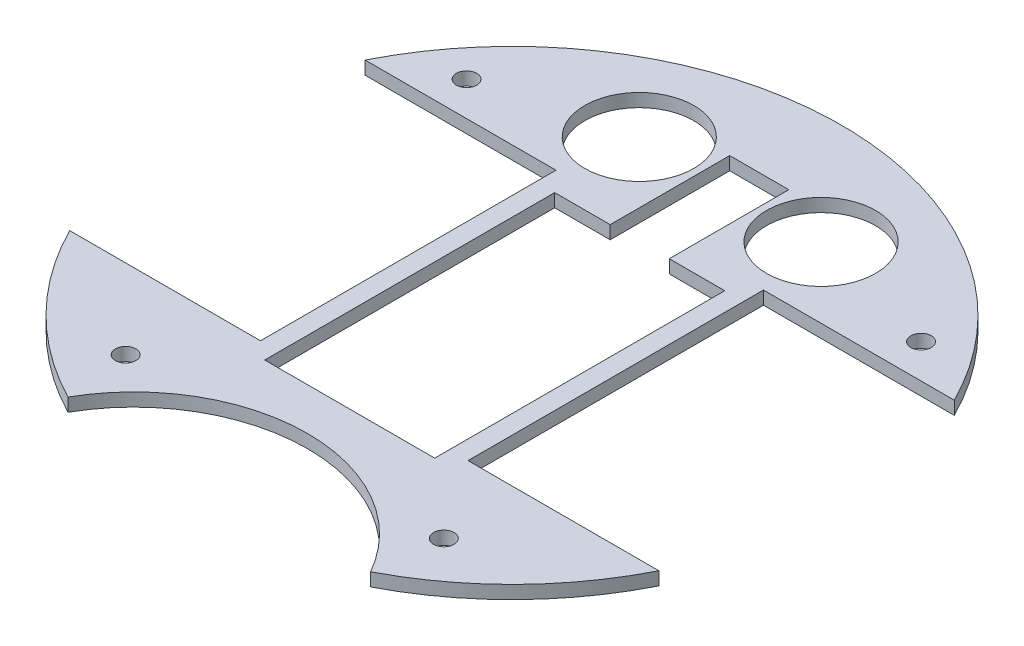
SolidWorks part; units mm, degrees
material "Acrylic (Medium-high impact)"
ref_plane "Front Plane" through (0, 0, 0) normal (0, 0, 1) x (1, 0, 0)
ref_plane "Top Plane" through (0, 0, 0) normal (0, 1, 0) x (1, 0, 0)
ref_plane "Right Plane" through (0, 0, 0) normal (1, 0, 0) x (0, 0, -1)
sketch "Sketch1" plane through (0, 0, 0) normal (0, 1, 0) x (1, 0, 0)
  line L0 (0, -83.2398) -> (-33.2911, -64.4046) construction
  line L1 (0, -83.2398) -> (0, 0) construction
  arc A0 (33.2911, -64.4046) -> (-33.2911, -64.4046) centre (0, 0) ccw
  arc A1 (33.2911, -64.4046) -> (-33.2911, -64.4046) centre (0, -83.2398) ccw
  dimension "D1" = 145
  dimension "D2" = 76.5
  dimension "D3" = 60.5
extrude "Boss-Extrude1" add sketch "Sketch1" along normal blind 2.9
sketch "solenoid placement" plane through (0, 2.9, 0) normal (0, 1, 0) x (1, 0, 0)
  line L4 (-18.7, -35.7) -> (18.7, -35.7)
  line L5 (18.7, -35.7) -> (18.7, 28.1)
  line L6 (18.7, 28.1) -> (-18.7, 28.1)
  line L7 (-18.7, 28.1) -> (-18.7, -35.7)
  line L8 (-18.7, -35.7) -> (18.7, -35.7)
  line L9 (18.7, -35.7) -> (18.7, 28.1)
  line L10 (18.7, 28.1) -> (-18.7, 28.1)
  line L11 (-18.7, 28.1) -> (-18.7, -35.7)
  circle A1 centre (0, 0) radius 72.5 construction
  arc A2 (33.2911, -64.4046) -> (-33.2911, -64.4046) centre (0, 0) ccw construction
  dimension "D1" = 0
extrude "Cut-Extrude1" cut sketch "solenoid placement" against normal through all
sketch "Sketch3" plane through (0, 2.9, 0) normal (0, 1, 0) x (1, 0, 0)
  line L4 (-34.63, -32.5) -> (-22.83, -32.5)
  line L5 (-22.83, -32.5) -> (-22.83, 32.5)
  line L6 (-22.83, 32.5) -> (-64.8074, 32.5)
  line L7 (-64.8074, -32.5) -> (-34.63, -32.5)
  line L8 (-34.63, -32.5) -> (-22.83, -32.5)
  line L9 (-22.83, -32.5) -> (-22.83, 32.5)
  line L10 (-22.83, 32.5) -> (-64.8074, 32.5)
  line L11 (-64.8074, -32.5) -> (-34.63, -32.5)
  line L12 (34.63, -32.5) -> (64.8074, -32.5)
  line L13 (64.8074, 32.5) -> (22.83, 32.5)
  line L14 (22.83, 32.5) -> (22.83, -32.5)
  line L15 (22.83, -32.5) -> (34.63, -32.5)
  line L16 (34.63, -32.5) -> (64.8074, -32.5)
  line L17 (64.8074, 32.5) -> (22.83, 32.5)
  line L18 (22.83, 32.5) -> (22.83, -32.5)
  line L19 (22.83, -32.5) -> (34.63, -32.5)
  arc A2 (-64.8074, 32.5) -> (-64.8074, -32.5) centre (0, 0) ccw
  arc A3 (-64.8074, 32.5) -> (-64.8074, -32.5) centre (0, 0) ccw
  arc A4 (64.8074, -32.5) -> (64.8074, 32.5) centre (0, 0) ccw
  arc A5 (64.8074, -32.5) -> (64.8074, 32.5) centre (0, 0) ccw
  dimension "D2" = 0
  dimension "D1" = 0
extrude "Cut-Extrude3" cut sketch "Sketch3" against normal through all
sketch "Sketch4" plane through (0, 2.9, 0) normal (0, 1, 0) x (1, 0, 0)
  line L0 (18.7, 28.1) -> (-18.7, 28.1) construction
  line L1 (-6.5, 28.1) -> (6.5, 28.1)
  line L2 (-6.5, 28.1) -> (-6.5, 54.4)
  line L3 (6.5, 54.4) -> (-6.5, 54.4) construction
  line L4 (6.5, 28.1) -> (6.5, 54.4)
  line L5 (6.5, 54.4) -> (-6.5, 54.4)
  point P6 (0, 28.1)
extrude "Cut-Extrude4" cut sketch "Sketch4" against normal through all
sketch "Sketch5" plane through (0, 2.9, 0) normal (0, 1, 0) x (1, 0, 0)
  circle A2 centre (-20, 48) radius 12
  circle A3 centre (-20, 48) radius 12
  circle A4 centre (20, 48) radius 12
  circle A21 centre (20, 48) radius 12
  dimension "D1" = 0
  dimension "D2" = 0
extrude "Cut-Extrude5" cut sketch "Sketch5" against normal through all
sketch "Sketch6" plane through (0, 2.9, 0) normal (0, 1, 0) x (1, 0, 0)
  circle A1 centre (35, -50) radius 2.25
  circle A2 centre (35, -50) radius 2.25
  circle A3 centre (-35, -50) radius 2.25
  circle A4 centre (-35, -50) radius 2.25
  circle A5 centre (-50, 40) radius 2.25
  circle A6 centre (-50, 40) radius 2.25
  circle A7 centre (50, 40) radius 2.25
  circle A8 centre (50, 40) radius 2.25
  dimension "D1" = 0
  dimension "D2" = 0
  dimension "D3" = 0
  dimension "D4" = 0
extrude "Cut-Extrude6" cut sketch "Sketch6" against normal through all
equation "\"smallPulleyTeeth\"= 15"
equation "\"largePulleyTeeth\"= 30"
equation "\"eighthThick\"= 2.9mm"
equation "\"sixteenthThick\" = 1.7mm"
equation "\"quarterThick\"=5.9mm"
equation "\"OD\" = 145mm"
equation "\"puckAngle\" = 60.5deg"
equation "\"D1@Sketch1\"=\"OD\""
equation "\"puckDiam\" = 76.5mm"
equation "\"D2@Sketch1\"=\"puckDiam\""
equation "\"D3@Sketch1\"=\"puckAngle\""
equation "\"D1@Boss-Extrude1\"=\"eighthThick\""
equation "\"axlePress\" = 5.9mm"
equation "\"press\" = 0.2mm"
equation "\"wheelClear\" = 0.3mm"
equation "\"10-32clear\" = 4.5mm"
equation "\"6-32clear\" = 3.3mm"
equation "\"8-32clear\" = 4.0mm"
equation "\"wheelHeight\" = 22mm"
equation "\"wheelWell\" = 65mm"
